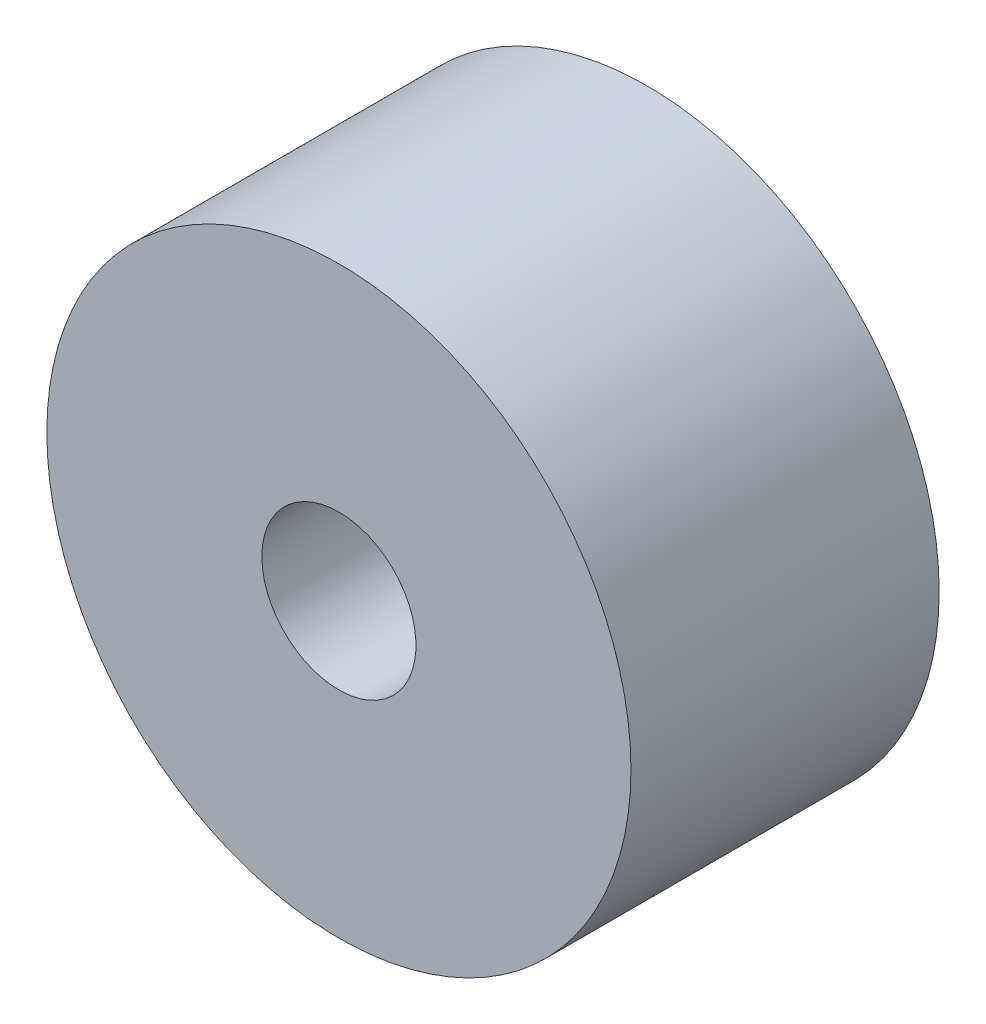
SolidWorks part; units mm, degrees
material "ABS"
ref_plane "前基準面" through (0, 0, 0) normal (0, 0, 1) x (1, 0, 0)
ref_plane "上基準面" through (0, 0, 0) normal (0, 1, 0) x (1, 0, 0)
ref_plane "右基準面" through (0, 0, 0) normal (1, 0, 0) x (0, 0, -1)
sketch "草圖1" plane through (0, 0, 0) normal (0, 0, 1) x (1, 0, 0)
  circle A0 centre (0, 0) radius 2.15
  circle A1 centre (0, 0) radius 8.15
  dimension "D1" = 4.3
  dimension "D2" = 6
extrude "填料-伸長1" add sketch "草圖1" along normal blind 8.6
sketch "草圖2" plane through (0, 0, 0) normal (0, 0, -1) x (-1, 0, 0)
  circle A0 centre (0, 0) radius 2.15
  circle A1 centre (0, 0) radius 3.65
  dimension "D1" = 4.3
  dimension "D2" = 1.5
extrude "填料-伸長2" add sketch "草圖2" along normal blind 1
chamfer "導角1" distance 1 angle 45 1 edges at (3.65, 0, 0)
